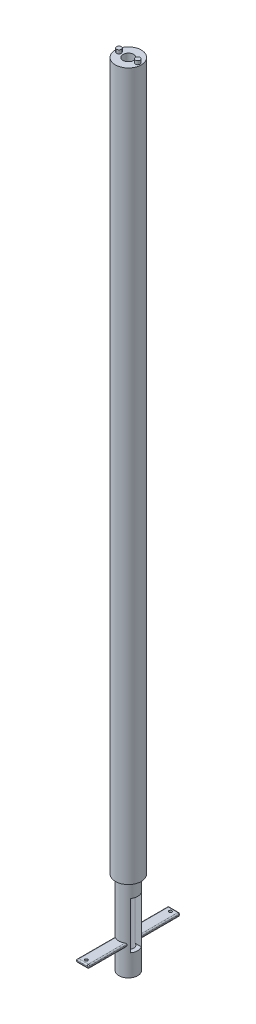
SolidWorks part; units mm, degrees
ref_plane "Front Plane" through (0, 0, 0) normal (0, 0, 1) x (1, 0, 0)
ref_plane "Top Plane" through (0, 0, 0) normal (0, 1, 0) x (1, 0, 0)
ref_plane "Right Plane" through (0, 0, 0) normal (1, 0, 0) x (0, 0, -1)
sketch "Sketch31" plane through (0, 0, 0) normal (0, 0, 1) x (1, 0, 0)
  line L0 (0, 0) -> (0, 35.4702)
sweep "Sweep3" add path "Sketch31" circular profile diameter 8 parameters "D3"=8
sketch "Sketch38" plane through (0, 0, 0) normal (0, 0, 1) x (1, 0, 0)
  line L1 (4, 35.4702) -> (-4, 35.4702) construction
  line L2 (0, 35.4702) -> (0, 336.2875)
sweep "Sweep4" add path "Sketch38" circular profile diameter 11 parameters "D3"=11
sketch "Sketch45" plane through (0, 0, 0) normal (0, 1, 0) x (1, 0, 0)
  circle A0 centre (0, 0) radius 2.25
extrude "Cut-Extrude2" cut sketch "Sketch45" along normal through all
sketch3d "3DSketch1"
  line L1 (0, 336.2875, 0) -> (0, 0, 0) construction
  line L2 (0, 336.2875, 0) -> (2.25, 336.2875, 0)
  line L18 (-5.5, 336.2875, 0) -> (-5.5, 336.2875, -5.5)
  line L19 (-5.5, 336.2875, -5.5) -> (0, 336.2875, -5.5)
  line L20 (0, 336.2875, -5.5) -> (5.5, 336.2875, -5.5)
  line L21 (5.5, 336.2875, -5.5) -> (5.5, 336.2875, 0)
  line L22 (0, 336.2875, 5.5) -> (5.5, 336.2875, 5.5)
  line L23 (5.5, 336.2875, 5.5) -> (5.5, 336.2875, 0)
  line L24 (0, 336.2875, 5.5) -> (-5.5, 336.2875, 5.5)
  line L25 (-5.5, 336.2875, 5.5) -> (-5.5, 336.2875, 0)
  circle A0 centre (0, 336.2875, 0) radius 2.25
  circle A1 centre (0, 336.2875, 0) radius 5.5 construction
  point P3 (0, 338.5375, 0)
  point P6 (0, 341.7875, 0)
  dimension "D1" = 5.5
  dimension "D3" = 5.5
  dimension "D2" = 5.5
  dimension "D4" = 5.5
  dimension "D5" = 5.5
  dimension "D6" = 5.5
  dimension "D7" = 5.5
  dimension "D8" = 5.5
sketch3d "3DSketch4"
  line L0 (4, 336.2875, 0) -> (4, 337.7875, 0)
  line L1 (-4.125, 336.2875, 0) -> (-4.125, 337.7875, 0)
  point P5 (-4.125, 336.2875, 0)
  point P6 (4, 336.2875, 0)
  dimension "D1" = 1.5
  dimension "D2" = 1.5
  dimension "D3" = 4
sweep "Sweep5" add path "3DSketch4" circular profile diameter 2 parameters "D3"=2
sketch3d "3DSketch5"
  line L0 (-4, 336.2875, 0) -> (-4, 337.7875, 0)
  line L1 (-5.5, 336.2875, 0) -> (-2.5, 336.2875, 0)
  line L2 (-4, 336.2875, 0) -> (-2.5, 336.2875, 0)
  dimension "D1" = 1.5
  dimension "D2" = 4
sweep "Sweep6" add path "3DSketch5" circular profile diameter 2 parameters "D3"=2
sketch "Sketch72" plane through (0, 0, 0) normal (1, 0, 0) x (0, 0, -1)
  line L0 (-2.318, 9.2361) -> (2.182, 9.2361)
  line L2 (-2.318, 9.2361) -> (-2.318, 29.2361)
  line L3 (-2.318, 29.2361) -> (2.182, 29.2361)
  line L4 (2.182, 29.2361) -> (2.182, 9.2361)
  dimension "D1" = 20
  dimension "D2" = 4.5
extrude "Cut-Extrude6" cut sketch "Sketch72" along normal blind 20
sketch "Sketch73" plane through (0, 0, 0) normal (0, 0, 1) x (1, 0, 0)
  line L0 (3, 337.7212) -> (4.3306, 337.589)
  line L1 (3, 337.7875) -> (3, 336.2875) construction
sketch "Sketch74" plane through (0, 0, 0) normal (0, 0, 1) x (1, 0, 0)
  point P5 (0, 12.0702)
sketch "Sketch76" plane through (0, 0, 0) normal (1, 0, 0) x (0, 0, -1)
  line L0 (3, 11.3702) -> (3, 12.7702)
  line L2 (-3, 12.0702) -> (-3, 12.7702)
  line L3 (3, 12.7702) -> (19.5, 12.7702)
  line L4 (-4, 35.4702) -> (4, 35.4702) construction
  line L5 (-3, 12.0702) -> (-3, 11.3702)
  line L6 (19.5, 11.3702) -> (19.5, 12.7702)
  line L7 (-19.5, 12.3702) -> (-19.5, 11.3702)
  line L8 (-19.5, 11.3702) -> (-3, 11.3702)
  line L9 (-19.5, 12.3702) -> (-19.5, 12.7702)
  line L10 (-19.5, 12.7702) -> (-3, 12.7702)
  line L12 (19.5, 11.3702) -> (3, 11.3702)
  line L14 (-3, 12.0702) -> (-3, 35.4702)
  dimension "D1" = 23.4
  dimension "D5" = 0.7
  dimension "D6" = 1.4
  dimension "D7" = 1.4
extrude "Boss-Extrude1" add sketch "Sketch76" along normal blind 2.5 and the other way blind 2.5 contours L10 L2 L5 L8 L7 L9
extrude "Boss-Extrude3" add sketch "Sketch76<4>" along normal blind 2.5 and the other way blind 2.5 contours L12 L6 L3 L0 region at (0, 12.0702, -11.25)
sketch "Sketch76<4>" plane through (0, 0, 0) normal (1, 0, 0) x (0, 0, -1) same geometry as "Sketch76"
sketch "Sketch77" plane through (0, 0, 0) normal (0, 1, 0) x (1, 0, 0)
  line L0 (-6.05, 0) -> (6.05, 0) construction
  circle A0 centre (0, 17.9) radius 0.6122
  circle A1 centre (0, -17.9) radius 0.6122
extrude "Cut-Extrude7" cut sketch "Sketch77" along normal blind 20
fillet "Fillet1" radius 0.5 14 edges at (-2.5, 12.7702, 11.3112) (-2.5, 11.3702, 11.3112) (2.5, 12.0702, 19.5) (0, 11.3702, 19.5) (2.5, 11.3702, 11.3112) (2.5, 12.7702, 11.3112) (0, 12.7702, 19.5) (-2.5, 11.3702, -11.3112) (-2.5, 12.7702, -11.3112) (0, 12.7702, -19.5) (0, 11.3702, -19.5) (2.5, 12.0702, -19.5) (2.5, 11.3702, -11.3112) (2.5, 12.7702, -11.3112)
sketch "Sketch84" plane through (0, 336.2875, 0) normal (0, 1, 0) x (1, 0, 0)
  line L0 (0, 0) -> (0, 4)
  line L1 (0, 0) -> (0, -4)
  circle A0 centre (0, 4) radius 1
  circle A1 centre (0, -4) radius 1
  dimension "D3" = 2
  dimension "D4" = 2
  dimension "D1" = 4
  dimension "D2" = 4
sketch "Sketch85" plane through (0, 337.7875, 0) normal (0, 1, 0) x (1, 0, 0)
  circle A0 centre (0, 0) radius 5.5
